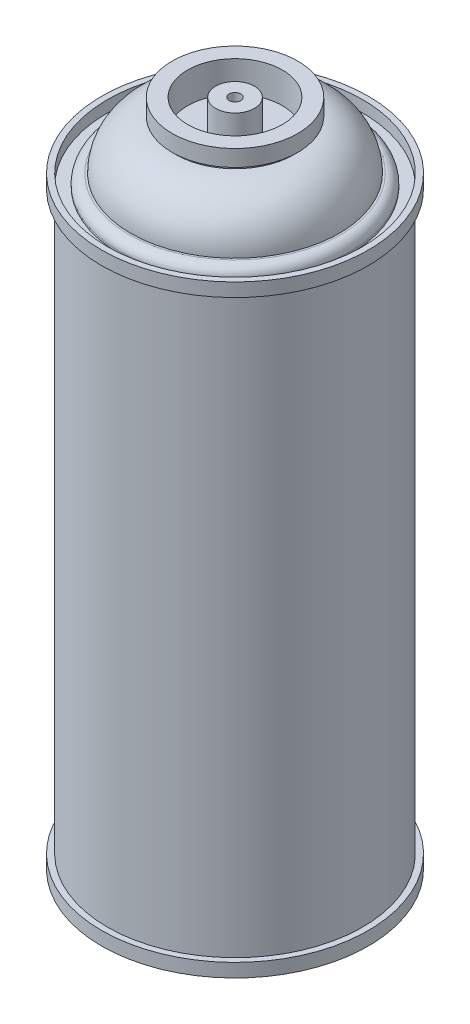
SolidWorks part; units mm, degrees
ref_plane "Front" through (0, 0, 0) normal (0, 0, 1) x (1, 0, 0)
ref_plane "Top" through (0, 0, 0) normal (0, 1, 0) x (1, 0, 0)
ref_plane "Right" through (0, 0, 0) normal (1, 0, 0) x (0, 0, -1)
sketch "Sketch1" plane through (0, 0, 0) normal (0, 1, 0) x (1, 0, 0)
  circle A0 centre (0, 0) radius 33
  dimension "D1" = 66
extrude "Boss-Extrude1" add sketch "Sketch1" along normal blind 156
sketch "Sketch2" plane through (0, 0, 0) normal (1, 0, 0) x (0, 0, -1)
  line L0 (33, 156) -> (27, 156) construction
  line L1 (33, 156) -> (-33, 156) construction
  line L2 (15.25, 167.75) -> (15.25, 168.75)
  line L3 (15.25, 168.75) -> (16.25, 168.75)
  line L4 (16.25, 168.75) -> (16.25, 173)
  line L5 (16.25, 173) -> (12.25, 173)
  line L6 (12.25, 173) -> (12.25, 165)
  line L7 (12.25, 165) -> (5, 165)
  line L8 (5, 165) -> (5, 173)
  line L9 (5, 173) -> (0, 173)
  line L10 (0, 173) -> (0, 156)
  line L11 (27, 156) -> (0, 156)
  arc A0 (27, 156) -> (15.25, 167.75) centre (15.25, 156) ccw
  dimension "D1" = 17
  dimension "D2" = 6
  dimension "D3" = 16.25
  dimension "D4" = 4
  dimension "D5" = 5
  dimension "D6" = 8
  dimension "D7" = 1
revolve "Revolve1" add sketch "Sketch2" angle 360 about L10
sketch "Sketch3" plane through (0, 156, 0) normal (0, 1, 0) x (1, 0, 0)
  circle A0 centre (0, 0) radius 34.5
  dimension "D1" = 69
extrude "Boss-Extrude2" add sketch "Sketch3" against normal blind 3.5
pattern_linear "LPattern1" count 2 spacing 152.5 along (0, -1, 0) of "Boss-Extrude2"
sketch "Sketch5" plane through (0, 0, 0) normal (0, 0, 1) x (1, 0, 0)
  line L0 (0, 0) -> (-32.5, 0)
  line L1 (-34.5, 0) -> (34.5, 0) construction
  line L2 (0, 12) -> (0, 0)
  arc A0 (-32.5, 0) -> (0, 12) centre (0, -38.0104) cw
  point P0 (0, 0)
  dimension "D1" = 12
  dimension "D2" = 2
revolve "Cut-Revolve1" cut sketch "Sketch5" angle 360 about L2
sketch "Sketch6" plane through (0, 173, 0) normal (0, 1, 0) x (1, 0, 0)
  circle A0 centre (0, 0) radius 1.5
  dimension "D1" = 3
extrude "Cut-Extrude1" cut sketch "Sketch6" against normal blind 3.5
sketch "Sketch7" plane through (0, 156, 0) normal (0, 1, 0) x (1, 0, 0)
  circle A0 centre (0, 0) radius 33
  circle A1 centre (0, 0) radius 30
  circle A2 centre (0, 0) radius 34.5 construction
  dimension "D1" = 1.5
  dimension "D2" = 3
extrude "Cut-Extrude2" cut sketch "Sketch7" against normal blind 3
fillet "Fillet1" radius 2.5 1 edges at (0, 156, 30)
